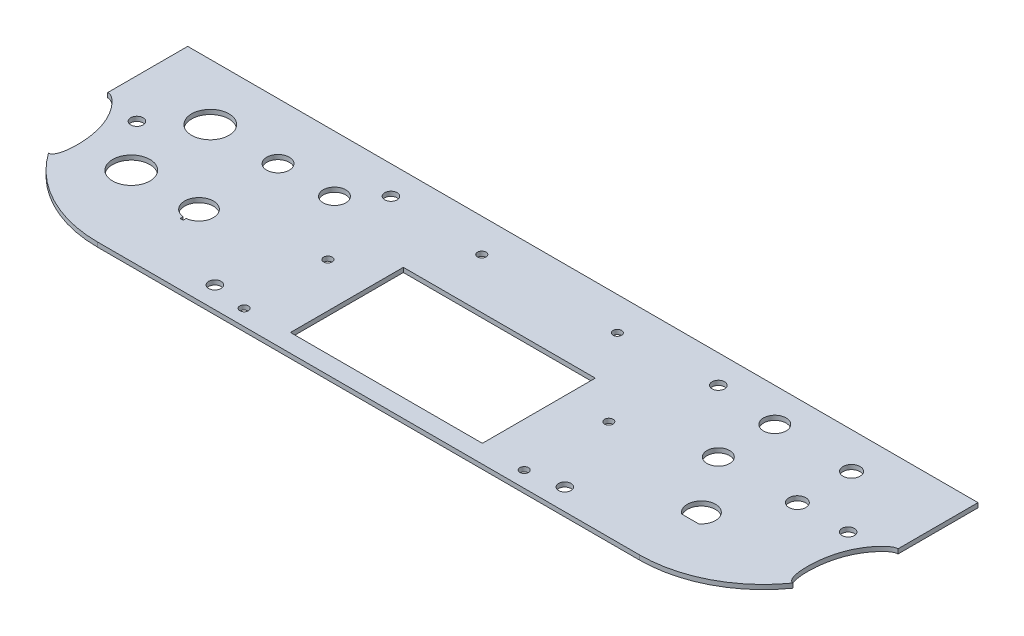
SolidWorks part; units mm, degrees
material "Thornel Mat VMA"
ref_plane "Front Plane" through (0, 0, 0) normal (0, 0, 1) x (1, 0, 0)
ref_plane "Top Plane" through (0, 0, 0) normal (0, 1, 0) x (1, 0, 0)
ref_plane "Right Plane" through (0, 0, 0) normal (1, 0, 0) x (0, 0, -1)
sketch "Sketch1" plane through (0, 0, 0) normal (0, 1, 0) x (1, 0, 0)
  line L13 (-222.25, 0) -> (222.25, 0) construction
  line L14 (222.25, -14.6125) -> (222.25, 36.1875)
  line L15 (222.25, 36.1875) -> (-222.25, 36.1875)
  line L16 (-222.25, -14.6125) -> (-222.25, 36.1875)
  line L18 (0, -95.4736) -> (0, 95.4736) construction
  line L19 (152.4, -84.4625) -> (-152.4, -84.4625)
  arc A0 (222.25, -14.6125) -> (152.4, -84.4625) centre (152.4, -14.6125) cw
  arc A1 (-152.4, -84.4625) -> (-222.25, -14.6125) centre (-152.4, -14.6125) cw
  point P10 (0, 0)
  point P16 (0, 0)
  point P17 (0, -84.4625)
  dimension "D1" = 50.8
  dimension "D2" = 444.5
  dimension "D3" = 304.8
  dimension "D5" = 120.65
  dimension "D6" = 36.1875
extrude "Boss-Extrude1" add sketch "Sketch1" along normal blind 2.54
sketch "Sketch2" plane through (0, 2.54, 0) normal (0, 1, 0) x (1, 0, 0)
  line L1 (53.975, -74.3025) -> (-53.975, -74.3025)
  line L2 (53.975, -74.3025) -> (53.975, -10.8025)
  line L3 (53.975, -10.8025) -> (-53.975, -10.8025)
  line L4 (-53.975, -74.3025) -> (-53.975, -10.8025)
  line L5 (53.975, -74.3025) -> (-53.975, -10.8025) construction
  line L6 (53.975, -10.8025) -> (-53.975, -74.3025) construction
  line L8 (-152.4, -84.4625) -> (152.4, -84.4625) construction
  point P0 (0, -42.5525)
  dimension "D1" = 63.5
  dimension "D2" = 10.16
  dimension "D3" = 107.95
extrude "Cut-Extrude1" cut sketch "Sketch2" against normal through all
sketch "Sketch4" plane through (0, 2.54, 0) normal (0, 1, 0) x (1, 0, 0)
  line L6 (-140.55, -48.0677) -> (-140.55, -49.8125)
  line L12 (-140.55, -49.8125) -> (-138.85, -49.8125)
  line L14 (-138.85, -49.8125) -> (-138.85, -48.0677)
  line L16 (171.45, -14.6125) -> (127, -14.6125) construction
  line L17 (222.25, -14.6125) -> (222.25, 36.1875) construction
  line L18 (222.25, 36.1875) -> (-222.25, 36.1875) construction
  line L19 (-222.25, 36.1875) -> (-222.25, -14.6125) construction
  line L21 (153.9875, -52.7125) -> (144.4625, -52.7125)
  line L22 (-152.4, -84.4625) -> (152.4, -84.4625) construction
  line L54 (87.5424, -0.6073) -> (87.4312, -0.6714)
  circle A0 centre (171.45, 15.8675) radius 4.7625
  circle A2 centre (-139.7, 4.4375) radius 6.35
  circle A3 centre (127, 17.1375) radius 6.35
  circle A4 centre (127, -14.6125) radius 6.35
  circle A6 centre (171.45, -14.6125) radius 4.7625
  circle A7 centre (-177.8, -40.0125) radius 10.5
  arc A8 (-138.85, -48.0677) -> (-140.55, -48.0677) centre (-139.7, -40.0125) ccw
  circle A9 centre (-177.8, 4.4375) radius 10.5
  arc A12 (153.9875, -52.7125) -> (144.4625, -52.7125) centre (149.225, -46.3625) ccw
  circle A25 centre (-107.95, 4.4375) radius 6.35
  arc A72 (85, -6.1987) -> (84.9641, -5.581) centre (79.666, -6.1987) ccw
  point P3 (149.225, -14.6125)
  point P10 (0, 0)
  point P11 (0, 0)
  point P24 (-139.7, -49.8125)
  dimension "D2" = 12.7
  dimension "D3" = 15.875
  dimension "D11" = 9.8
  dimension "D12" = 16.2
  dimension "D20" = 38.1
  dimension "D25" = 9.525
  dimension "D10" = 21
  dimension "D4" = 31.75
  dimension "D5" = 20.32
  dimension "D6" = 50.8
  dimension "D7" = 44.45
  dimension "D8" = 31.75
  dimension "D9" = 50.8
  dimension "D13" = 44.45
  dimension "D14" = 82.55
  dimension "D16" = 31.75
  dimension "D17" = 76.2
  dimension "D18" = 6.35
  dimension "D19" = 1.7
  dimension "D21" = 31.75
sketch "Sketch5" plane through (0, 2.54, 0) normal (0, 1, 0) x (1, 0, 0)
  line L0 (222.25, -14.6125) -> (222.25, 36.1875) construction
  line L1 (0, -1.397) -> (0, 1.397) construction
  arc A0 (152.4, -84.4625) -> (222.25, -14.6125) centre (152.4, -14.6125) ccw construction
  spline S0 degree 3 poles (235.1366, 7.4285) (207.1804, -83.7935) (202.3049, -25.2668) (235.1366, 7.4285) (207.1804, -83.7935) (202.3049, -25.2668) knots -1 -0.674196 -0.483325 0 0.325804 0.516675 1 1.325804 1.516675 2 only from (209.4403, -54.9291) to (209.4403, -54.9291)
  spline S1 degree 3 poles (-235.1366, 7.4285) (-207.1804, -83.7935) (-202.3049, -25.2668) (-235.1366, 7.4285) (-207.1804, -83.7935) (-202.3049, -25.2668) knots -1 -0.674196 -0.483325 0 0.325804 0.516675 1 1.325804 1.516675 2 only from (-209.4403, -54.9291) to (-209.4403, -54.9291)
  line M8 (-222.25, 36.1875) -> (-222.25, -14.6125)
  arc M9 (-222.25, -14.6125) -> (-152.4, -84.4625) centre (-152.4, -14.6125) ccw
extrude "Cut-Extrude4" cut sketch "Sketch5" against normal up to surface (2.54 mm away) contours S1 M9 M8 | S0 region at (-213.6132, 2.54, 31.5069) up to face at (0, 0, 42.5525)
extrude "Cut-Extrude3" cut sketch "Sketch4" against normal through all contours A25 | A9 | A8 L6 L12 L14 | A7 | A6 | A0 | A3 | A2 | A12 L21 | A4 region at (-107.95, 2.54, -4.4375)
sketch "Sketch6" plane through (0, 0, 0) normal (0, -1, 0) x (1, 0, 0)
  line L0 (0, -1.397) -> (0, 1.397) construction
  line L1 (222.25, -36.1875) -> (-222.25, -36.1875) construction
  line L2 (222.25, 8.8296) -> (222.25, -36.1875) construction
  line L3 (92.075, -20.32) -> (-92.075, -20.32) construction
  line L4 (98.425, 72.39) -> (-98.425, 72.39) construction
  line L5 (0, 72.39) -> (0, -20.32) construction
  circle A0 centre (92.075, -20.32) radius 3 construction
  circle A1 centre (98.425, 72.39) radius 3 construction
  circle A2 centre (200.025, 14.6125) radius 3 construction
  circle A3 centre (-92.075, -20.32) radius 3 construction
  circle A4 centre (-200.025, 14.6125) radius 3 construction
  circle A5 centre (-98.425, 72.39) radius 3 construction
  point P0 (92.075, -20.32)
  point P2 (200.025, 14.6125)
  point P3 (98.425, 72.39)
  point P8 (-92.075, -20.32)
  point P10 (-200.025, 14.6125)
  point P12 (-98.425, 72.39)
  point P27 (-92.075, -20.32)
  point P33 (-98.425, 72.39)
  point P37 (98.425, 72.39)
  point P41 (92.075, -20.32)
  dimension "D1" = 50.8
  dimension "D7" = 6
  dimension "D2" = 22.225
  dimension "D3" = 184.15
  dimension "D4" = 196.85
  dimension "D5" = 72.39
  dimension "D6" = 20.32
hole_wizard "M6 Clearance Hole1" positions "Sketch6" profile "Sketch7" hole size "M6" standard "ANSI Metric" end condition through all
sketch "Sketch7" plane through (92.075, 0, -20.32) normal (1, 0, 0) x (0, 0, -1)
  line L0 (0, 0) -> (0, 2.54)
  line L1 (0, 2.54) -> (3.5, 2.54)
  line L2 (3.5, 2.54) -> (3.5, 0)
  line L5 (3.5, 0) -> (0, 0)
  line L11 (0, -6.35) -> (0, 107.95) construction
  dimension "Thru Hole Dia." = 7
  dimension "Thru Hole Depth" = 2.54
sketch "Sketch8" plane through (0, 2.54, 0) normal (0, 1, 0) x (1, 0, 0)
  point P0 (-78.7827, -75.5731)
  point P1 (-79, -28.2331)
  point P3 (-38.131, 17.4596)
  point P5 (38.131, 17.4596)
  point P7 (79, -28.2331)
  point P9 (78.7827, -75.5731)
hole_wizard "M4 Clearance Hole1" positions "Sketch8" profile "Sketch9" hole size "M4" standard "ANSI Metric" end condition through all
sketch "Sketch9" plane through (-78.7827, 2.54, 75.5731) normal (1, 0, 0) x (0, 0, 1)
  line L0 (0, 0) -> (0, 2.54)
  line L1 (0, 2.54) -> (2.4, 2.54)
  line L2 (2.4, 2.54) -> (2.4, 0)
  line L5 (2.4, 0) -> (0, 0)
  line L11 (0, -6.35) -> (0, 107.95) construction
  dimension "Thru Hole Dia." = 4.8
  dimension "Thru Hole Depth" = 2.54
